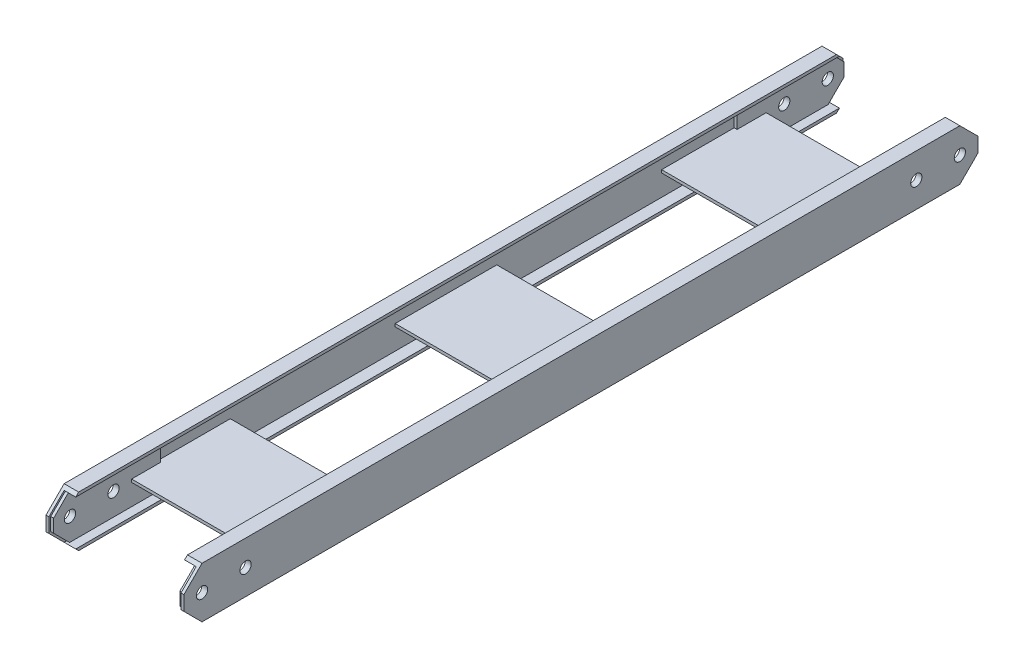
SolidWorks part; units mm, degrees
ref_plane "前视基准面" through (0, 0, 0) normal (0, 0, 1) x (1, 0, 0)
ref_plane "上视基准面" through (0, 0, 0) normal (0, 1, 0) x (1, 0, 0)
ref_plane "右视基准面" through (0, 0, 0) normal (1, 0, 0) x (0, 0, -1)
sketch "草图1" plane through (0, 0, 0) normal (0, 0, 1) x (1, 0, 0)
  line L0 (-1000, 0) -> (49000, 0) construction
  line L1 (-190, 70) -> (-150, 70)
  line L2 (-190, 70) -> (-190, -70)
  line L3 (-190, -70) -> (-150, -70)
  line L4 (-150, 70) -> (-150, -70)
  line L5 (0, -1000) -> (0, 49000) construction
  line L7 (-182, 62) -> (-150, 62)
  line L8 (-182, 62) -> (-182, -62)
  line L9 (-182, -62) -> (-150, -62)
  line L10 (-150, 62) -> (-150, -62)
  dimension "D1" = 140
  dimension "D2" = 8
  dimension "D3" = 8
  dimension "D4" = 40
  dimension "D5" = 70
  dimension "D6" = 190
  dimension "D7" = 8
extrude "拉伸1" add sketch "草图1" along normal blind 2189 contours L9 L8 L7 L4 L1 L2 L3 region at (-170, 68.544, 0)
sketch "草图2" plane through (-190, 0, 0) normal (-1, 0, 0) x (0, 0, 1)
  line L0 (-1000, 0) -> (49000, 0) construction
  line L1 (1094.5, -1070) -> (1094.5, 48930) construction
  line L2 (2189, -70) -> (0, -70) construction
  line L3 (0, 70) -> (0, -70) construction
  line L4 (50, 70) -> (0, 20)
  line L5 (2189, 70) -> (0, 70) construction
  line L6 (0, 20) -> (0, 70)
  line L7 (0, 70) -> (50, 70)
  line L8 (50, -70) -> (0, -20)
  line L9 (0, -20) -> (0, -70)
  line L10 (0, -70) -> (50, -70)
  line L11 (2189, -70) -> (2139, -70)
  line L12 (2189, -20) -> (2189, -70)
  line L13 (2139, -70) -> (2189, -20)
  line L14 (2189, 70) -> (2139, 70)
  line L15 (2189, 20) -> (2189, 70)
  line L16 (2139, 70) -> (2189, 20)
  line L17 (954.5, -4) -> (1234.5, -4)
  line L18 (220, 4) -> (500, 4)
  line L19 (220, 4) -> (220, -4)
  line L20 (220, -4) -> (500, -4)
  line L21 (500, 4) -> (500, -4)
  line L22 (954.5, 4) -> (1234.5, 4)
  line L23 (954.5, 4) -> (954.5, -4)
  line L24 (1234.5, 4) -> (1234.5, -4)
  line L25 (1689, -4) -> (1969, -4)
  line L26 (1689, 4) -> (1969, 4)
  line L27 (1689, 4) -> (1689, -4)
  line L28 (1969, 4) -> (1969, -4)
  line L29 (220, -4) -> (954.5, -4) construction
  circle A0 centre (50, 0) radius 15.5
  circle A1 centre (170, 0) radius 15.5
  circle A2 centre (2019, 0) radius 15.5
  circle A3 centre (2139, 0) radius 15.5
  point P8 (1094.5, -70)
  dimension "D2" = 31
  dimension "D1" = 50
  dimension "D3" = 120
  dimension "D4" = 50
  dimension "D5" = 50
  dimension "D6" = 50
  dimension "D7" = 50
  dimension "D8" = 280
  dimension "D9" = 8
  dimension "D10" = 4
  dimension "D11" = 220
  dimension "D12" = 734.5
extrude "拉伸3" cut sketch "草图2" against normal through all contours L9 L10 L8 | L4 L6 L7 | A0 | A1 | A2 | A3 | L16 L15 L14 | L13 L12 L11
sketch "草图3" plane through (-182, 0, 0) normal (1, 0, 0) x (0, 0, -1)
  line L0 (-3189, 0) -> (46811, 0) construction
  line L1 (-2189, 20) -> (-2189, -20) construction
  line L2 (-2184, -17.9289) -> (-2184, 17.9289)
  line L3 (-2189, -20) -> (-2147, -62) construction
  line L4 (-2184, -17.9289) -> (-2139.9289, -62)
  line L5 (-2139.9289, -62) -> (-1889, -62)
  line L6 (-2147, -62) -> (-42, -62) construction
  line L7 (-1889, -62) -> (-1889, 62)
  line L8 (-2139.9289, 62) -> (-1889, 62)
  line L9 (-2184, 17.9289) -> (-2139.9289, 62)
  line L10 (-1094.5, -1062) -> (-1094.5, 48938) construction
  line L11 (-5, -17.9289) -> (-49.0711, -62)
  line L12 (-49.0711, -62) -> (-300, -62)
  line L13 (-49.0711, 62) -> (-300, 62)
  line L14 (-5, 17.9289) -> (-49.0711, 62)
  line L15 (-5, -17.9289) -> (-5, 17.9289)
  line L16 (-300, -62) -> (-300, 62)
  point P5 (-2189, 0)
  point P15 (-1889, 0)
  point P17 (-2184, 0)
  point P20 (-1094.5, -62)
  dimension "D1" = 5
  dimension "D2" = 5
  dimension "D3" = 0
  dimension "D4" = 300
extrude "拉伸4" add sketch "草图3" along normal blind 8
extrude "拉伸5" cut sketch "草图2<6>" against normal through all contours A3 | A2 | A1 | A0
sketch "草图2<6>" plane through (-190, 0, 0) normal (-1, 0, 0) x (0, 0, 1) same geometry as "草图2"
extrude "拉伸6" add sketch "草图2<7>" against normal blind 190 contours L25 L28 L26 L27 | L17 L24 L22 L23 | L18 L21 L20 L19
sketch "草图2<7>" plane through (-190, 0, 0) normal (-1, 0, 0) x (0, 0, 1) same geometry as "草图2"
mirror "镜向1" about plane through (0, -4, 1689) normal (-1, 0, 0) of bodies 107
